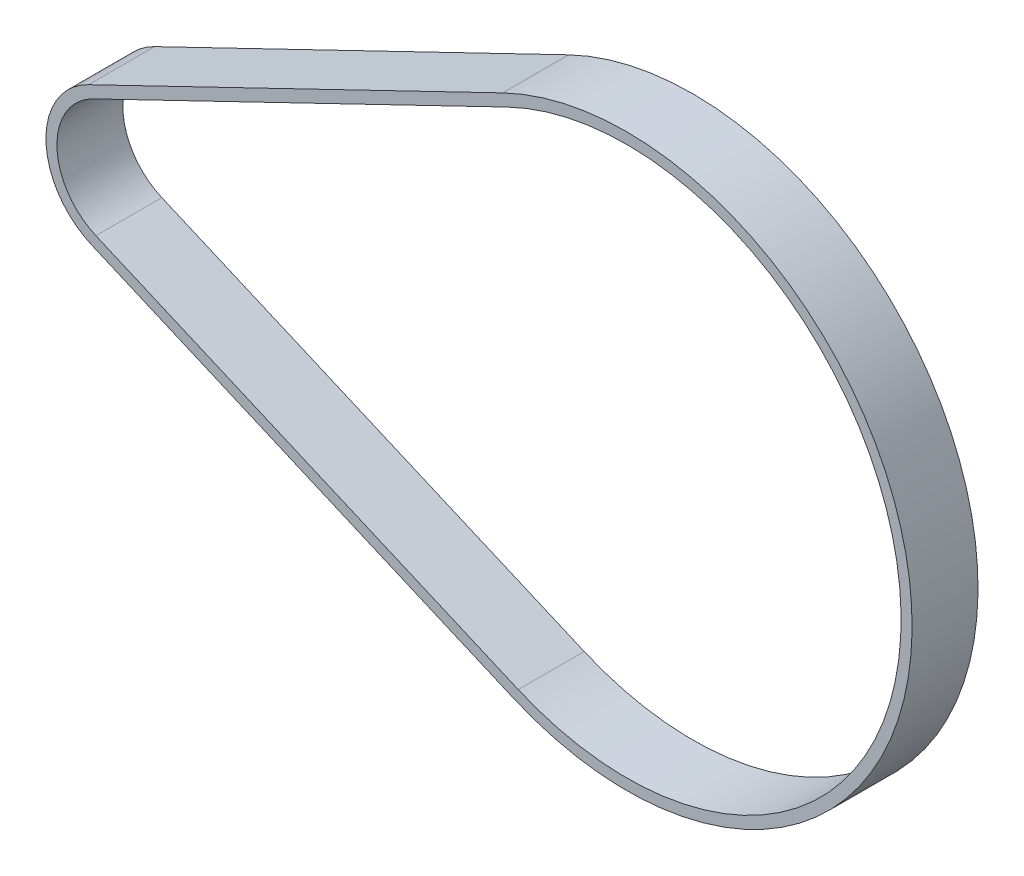
SolidWorks part; units mm, degrees
ref_plane "Front Plane" through (0, 0, 0) normal (0, 0, 1) x (1, 0, 0)
ref_plane "Top Plane" through (0, 0, 0) normal (0, 1, 0) x (1, 0, 0)
ref_plane "Right Plane" through (0, 0, 0) normal (1, 0, 0) x (0, 0, -1)
sketch "Sketch2" plane through (0, 0, 0) normal (0, 0, 1) x (1, 0, 0)
  line L0 (0, 0) -> (1, 0) construction
  line L1 (0, 0) -> (0, 1) construction
  line L4 (35.9214, -25.8937) -> (-2.51, -9.3453)
  line L5 (-2.7604, 2.2325) -> (34.9197, 20.4268)
  arc A1 (34.9197, 20.4268) -> (35.9214, -25.8937) centre (45.9925, -2.5048) cw
  arc A2 (-2.51, -9.3453) -> (-2.7604, 2.2325) centre (0.0073, -3.4993) cw
extrude "Extrude-Thin1" add sketch "Sketch2" against normal blind 6 from offset 1 thin offset against normal yes thin type mid plane wall 1
